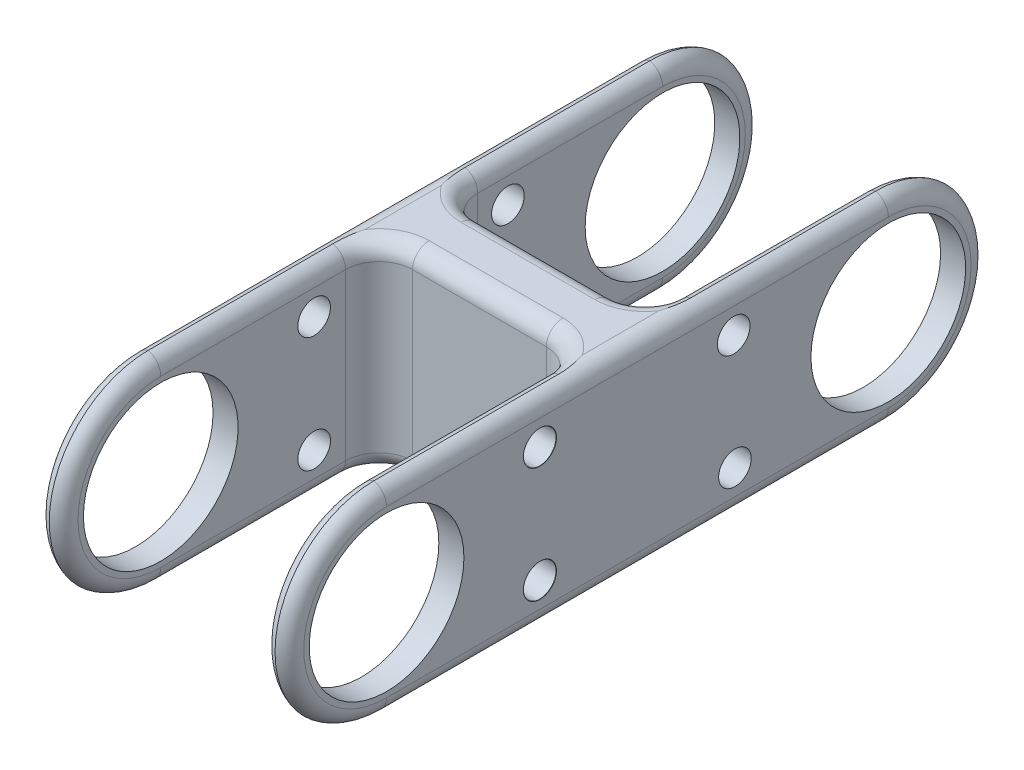
SolidWorks part; units mm, degrees
ref_plane "Front Plane" through (0, 0, 0) normal (0, 0, 1) x (1, 0, 0)
ref_plane "Top Plane" through (0, 0, 0) normal (0, 1, 0) x (1, 0, 0)
ref_plane "Right Plane" through (0, 0, 0) normal (1, 0, 0) x (0, 0, -1)
sketch "Sketch1" plane through (0, 0, 0) normal (1, 0, 0) x (0, 0, -1)
  line L0 (0, 11.9) -> (60, 11.9)
  line L1 (0, -11.9) -> (60, -11.9)
  line L2 (30, 11.9) -> (30, -11.9) construction
  circle A0 centre (0, 0) radius 9.25
  arc A1 (0, 11.9) -> (0, -11.9) centre (0, 0) ccw
  circle A2 centre (60, 0) radius 9.25
  arc A3 (60, 11.9) -> (60, -11.9) centre (60, 0) cw
  dimension "D1" = 18.5
  dimension "D2" = 23.8
  dimension "D3" = 60
extrude "Boss-Extrude1" add sketch "Sketch1" along normal blind 30
sketch "Sketch2" plane through (0, 11.9, 0) normal (0, 1, 0) x (1, 0, 0)
  line L0 (0, -11.9) -> (30, -11.9) construction
  line L1 (3, -11.9) -> (27, -11.9)
  line L2 (3, -11.9) -> (3, 26.1)
  line L3 (3, 26.1) -> (27, 26.1)
  line L4 (27, -11.9) -> (27, 26.1)
  line L5 (0, 30) -> (30, 30) construction
  line L6 (0, 60) -> (0, 0) construction
  line L7 (30, 60) -> (30, 0) construction
  line L8 (3, 33.9) -> (27, 33.9)
  line L9 (27, 71.9) -> (27, 33.9)
  line L10 (3, 71.9) -> (27, 71.9)
  line L11 (3, 71.9) -> (3, 33.9)
  dimension "D1" = 38
  dimension "D2" = 3
  dimension "D3" = 3
extrude "Cut-Extrude1" cut sketch "Sketch2" against normal through all
ref_plane "Plane1" through (0, 0, -30) normal (0, 0, 1) x (1, 0, 0)
fillet "Fillet1" radius 4 4 edges at (27, 0, -26.1) (3, 0, -26.1) (27, 0, -33.9) (3, 0, -33.9)
hole_wizard "M3.5 Clearance Hole1" positions "Sketch3" profile "Sketch4" hole size "M3.5" standard "ANSI Metric" end condition through all
sketch "Sketch3" plane through (0, 0, 0) normal (-1, 0, 0) x (0, 0, 1)
  circle A0 centre (-41.511, 6.9) radius 1.7024 construction
  point P0 (-41.66, -6.9)
  point P3 (-41.511, 6.9)
sketch "Sketch4" plane through (0, -6.9, -41.66) normal (0, 1, 0) x (0, 0, 1)
  line L0 (0, 0) -> (0, 30)
  line L1 (0, 30) -> (1.95, 30)
  line L2 (1.95, 30) -> (1.95, 0.025)
  line L3 (1.95, 0.025) -> (1.975, 0)
  line L5 (1.975, 0) -> (0, 0)
  line L6 (-1.95, 0.025) -> (-1.975, 0) construction
  line L11 (0, -6.35) -> (0, 107.95) construction
  dimension "Thru Hole Dia." = 3.9
  dimension "Thru Hole Depth" = 30
  dimension "Near C'Sink Dia." = 3.95
  dimension "Near C'Sink Angle" = 90
sketch "Sketch5" plane through (0, 0, -33.9) normal (0, 0, -1) x (-1, 0, 0)
  line L0 (-23, 11.9) -> (-23, -11.9) construction
  line L1 (-23, 0) -> (-7, 0) construction
  line L2 (-7, -11.9) -> (-7, 11.9) construction
  line B0 (-23, -3.65) -> (-23, -10.15)
  line B1 (-23, -3.65) -> (-20, -3.65)
  line B2 (-20, -3.65) -> (-20, -10.15)
  line B3 (-23, -10.15) -> (-20, -10.15)
  line B4 (-23, 0) -> (-7, 0) construction
  line B5 (-14.9675, -0.1255) -> (-15, -8.8352) construction
  line B6 (-7.01, -10.2096) -> (-10.0099, -10.1872)
  line B7 (-9.9615, -3.6874) -> (-10.0099, -10.1872)
  line B8 (-6.9616, -3.7098) -> (-9.9615, -3.6874)
  line B9 (-6.9616, -3.7098) -> (-7.01, -10.2096)
  line B10 (-6.9616, 3.7098) -> (-7.01, 10.2096)
  line B11 (-6.9616, 3.7098) -> (-9.9615, 3.6874)
  line B12 (-9.9615, 3.6874) -> (-10.0099, 10.1872)
  line B13 (-7.01, 10.2096) -> (-10.0099, 10.1872)
  line B14 (-23, 10.15) -> (-20, 10.15)
  line B15 (-20, 3.65) -> (-20, 10.15)
  line B16 (-23, 3.65) -> (-20, 3.65)
  line B17 (-23, 3.65) -> (-23, 10.15)
sketch_block_instance "Block1-1"
sketch_block "Block1" parameters "D1"=3, "D2"=6.5
sketch "Sketch6" plane through (30, 0, 0) normal (-1, 0, 0) x (0, 0, 1)
  line L0 (-39.685, -6.9) -> (-43.635, -6.9) construction
  circle A0 centre (-41.66, -6.9) radius 1.975 construction
hole_wizard "M3.5 Clearance Hole2" positions "Sketch9" profile "Sketch8" hole size "M3.5" standard "ANSI Metric" end condition through all
sketch "Sketch9" plane through (30, 0, 0) normal (1, 0, 0) x (0, 0, -1)
  circle A0 centre (18.34, -6.9) radius 1.975 construction
  circle A1 centre (18.34, 6.9) radius 1.975 construction
  circle A2 centre (18.34, -6.9) radius 1.975 construction
  circle A3 centre (18.34, 6.9) radius 1.975 construction
  point P0 (18.34, 6.9)
  point P3 (18.34, -6.9)
  point P12 (18.34, -6.9)
  point P13 (18.34, 6.9)
sketch "Sketch8" plane through (30, 6.9, -18.34) normal (0, 1, 0) x (0, 0, -1)
  line L0 (0, 0) -> (0, 30)
  line L1 (0, 30) -> (1.95, 30)
  line L2 (1.95, 30) -> (1.95, 0.025)
  line L3 (1.95, 0.025) -> (1.975, 0)
  line L5 (1.975, 0) -> (0, 0)
  line L6 (-1.95, 0.025) -> (-1.975, 0) construction
  line L11 (0, -6.35) -> (0, 107.95) construction
  dimension "Thru Hole Dia." = 3.9
  dimension "Thru Hole Depth" = 30
  dimension "Near C'Sink Dia." = 3.95
  dimension "Near C'Sink Angle" = 90
sketch "Sketch10" plane through (0, 0, -26.1) normal (0, 0, 1) x (1, 0, 0)
  line L0 (-1.0691, -12.5585) -> (14.9309, -12.5585) construction
  line L1 (23, 0) -> (7, 0) construction
  line L2 (23, -11.9) -> (23, 11.9) construction
  line L3 (7, 11.9) -> (7, -11.9) construction
  line B0 (7, -3.65) -> (7, -10.15)
  line B1 (7, -3.65) -> (10, -3.65)
  line B2 (10, -3.65) -> (10, -10.15)
  line B3 (7, -10.15) -> (10, -10.15)
  line B4 (7, 0) -> (23, 0) construction
  line B5 (15.0325, -0.1255) -> (15, -8.8352) construction
  line B6 (22.99, -10.2096) -> (19.9901, -10.1872)
  line B7 (20.0385, -3.6874) -> (19.9901, -10.1872)
  line B8 (23.0384, -3.7098) -> (20.0385, -3.6874)
  line B9 (23.0384, -3.7098) -> (22.99, -10.2096)
  line B10 (23.0384, 3.7098) -> (22.99, 10.2096)
  line B11 (23.0384, 3.7098) -> (20.0385, 3.6874)
  line B12 (20.0385, 3.6874) -> (19.9901, 10.1872)
  line B13 (22.99, 10.2096) -> (19.9901, 10.1872)
  line B14 (7, 10.15) -> (10, 10.15)
  line B15 (10, 3.65) -> (10, 10.15)
  line B16 (7, 3.65) -> (10, 3.65)
  line B17 (7, 3.65) -> (7, 10.15)
sketch_block_instance "Block1-2"
fillet "Fillet2" [suppressed] radius 2
hole_wizard "M3.5 Clearance Hole3" positions "Sketch11" profile "Sketch12" hole size "M3.5" standard "ANSI Metric" end condition through all
sketch "Sketch11" plane through (30, 0, 0) normal (1, 0, 0) x (0, 0, -1)
  point P0 (18.34, 6.9)
  point P3 (18.34, -6.9)
sketch "Sketch12" plane through (30, 6.9, -18.34) normal (0, 1, 0) x (0, 0, -1)
  line L0 (0, 0) -> (0, 30)
  line L1 (0, 30) -> (1.95, 30)
  line L2 (1.95, 30) -> (1.95, 0.025)
  line L3 (1.95, 0.025) -> (1.975, 0)
  line L5 (1.975, 0) -> (0, 0)
  line L6 (-1.95, 0.025) -> (-1.975, 0) construction
  line L11 (0, -6.35) -> (0, 107.95) construction
  dimension "Thru Hole Dia." = 3.9
  dimension "Thru Hole Depth" = 30
  dimension "Near C'Sink Dia." = 3.95
  dimension "Near C'Sink Angle" = 90
sketch "Sketch13" [suppressed] plane through (0, 0, 0) normal (-1, 0, 0) x (0, 0, 1)
  line L0 (-125.6084, 9.9) -> (-125.6084, -9.9) construction
  line L1 (0, 9.9) -> (-60, 9.9) construction
  line L2 (-60, -9.9) -> (0, -9.9) construction
  point P0 (-128.6084, 6.9)
  dimension "D1" = 3
fillet "Fillet3" radius 2 32 edges at (0, 0, -71.9) (0, -11.9, -30) (0, 0, 11.9) (3, 0, -71.9) (3, -11.9, -48.95) (4.1716, -11.9, -35.0716) (15, -11.9, -33.9) (25.8284, -11.9, -35.0716) (27, -11.9, -48.95) (27, 0, -71.9) (30, 0, -71.9) (30, -11.9, -30) (30, 0, 11.9) (27, 0, 11.9) (27, -11.9, -11.05) (25.8284, -11.9, -24.9284) (15, -11.9, -26.1) (4.1716, -11.9, -24.9284) (3, -11.9, -11.05) (3, 0, 11.9) (0, 11.9, -30) (3, 11.9, -48.95) (4.1716, 11.9, -35.0716) (15, 11.9, -33.9) (25.8284, 11.9, -35.0716) (27, 11.9, -48.95) (30, 11.9, -30) (27, 11.9, -11.05) (25.8284, 11.9, -24.9284) (15, 11.9, -26.1) (4.1716, 11.9, -24.9284) (3, 11.9, -11.05)
